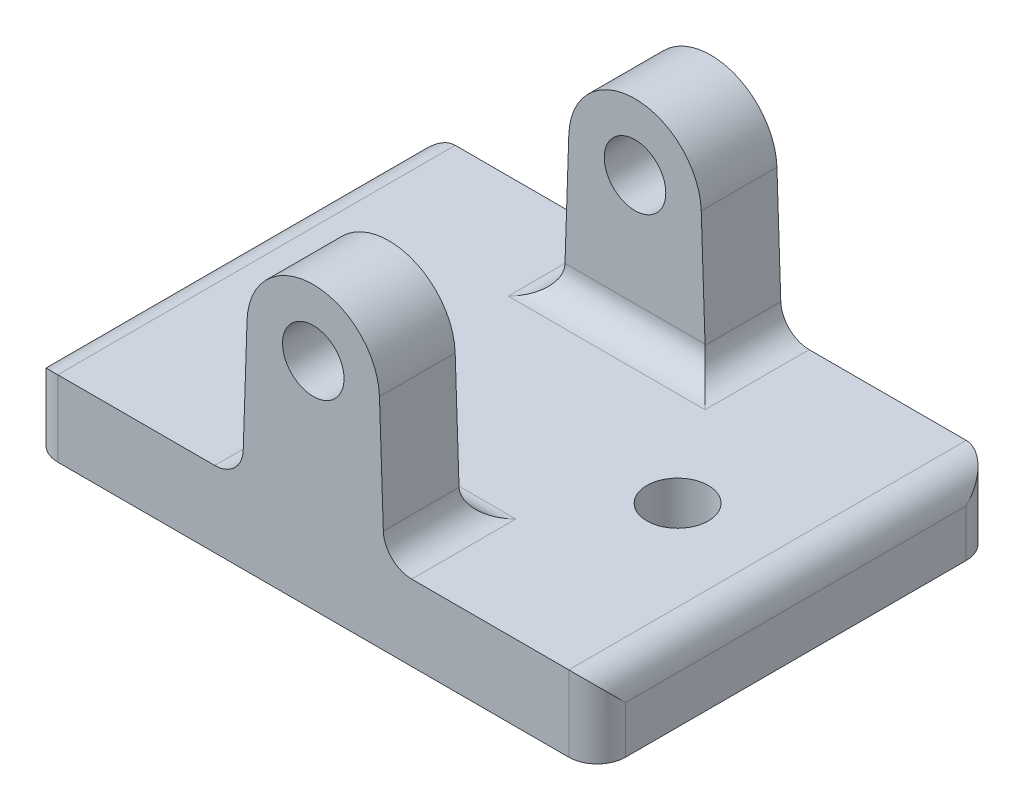
SolidWorks part; units mm, degrees
material "ABS"
ref_plane "Front Plane" through (0, 0, 0) normal (0, 0, 1) x (1, 0, 0)
ref_plane "Top Plane" through (0, 0, 0) normal (0, 1, 0) x (1, 0, 0)
ref_plane "Right Plane" through (0, 0, 0) normal (1, 0, 0) x (0, 0, -1)
sketch "Sketch2" plane through (0, 0, 0) normal (0, 1, 0) x (1, 0, 0)
  line L0 (-17.5, 0) -> (0, 0) construction
  line L1 (-30, -21) -> (30, -21)
  line L2 (-30, -21) -> (-30, 21)
  line L3 (-30, 21) -> (30, 21)
  line L4 (30, -21) -> (30, 21)
  line L5 (-30, -21) -> (30, 21) construction
  line L6 (-30, 21) -> (30, -21) construction
  line L7 (0, -55) -> (0, 55) construction
  circle A0 centre (-17.5, 0) radius 3.25
  circle A1 centre (17.5, 0) radius 3.25
  point P0 (0, 0)
  dimension "D4" = 6.5
  dimension "D1" = 42
  dimension "D2" = 60
  dimension "D3" = 17.5
extrude "Boss-Extrude1" add sketch "Sketch2" along normal blind 8
sketch "Sketch3" plane through (0, 0, 21) normal (0, 0, 1) x (1, 0, 0)
  line L0 (-7.5, 8) -> (-6.9961, 23)
  line L1 (-30, 8) -> (30, 8) construction
  line L2 (6.9961, 23) -> (7.5, 8)
  line L3 (-7.5, 8) -> (7.5, 8)
  arc A0 (-6.9961, 23) -> (6.9961, 23) centre (0, 22.765) cw
  circle A1 centre (0, 22.765) radius 3.25
  dimension "D1" = 7
  dimension "D4" = 6.5
  dimension "D2" = 15
  dimension "D3" = 15
extrude "Boss-Extrude2" add sketch "Sketch3" against normal blind 8
mirror "Mirror1" about plane through (0, 0, 0) normal (0, 0, 1) of "Boss-Extrude2"
fillet "Fillet1" radius 3 12 edges at (7.5, 8, -17) (7.5, 8, 17) (-7.5, 8, 17) (-7.5, 8, -17) (30, 8, 0) (0, 8, 13) (-30, 8, 0) (0, 8, -13) (30, 4, 21) (-30, 4, 21) (-30, 4, -21) (30, 4, -21) tangent propagation no
